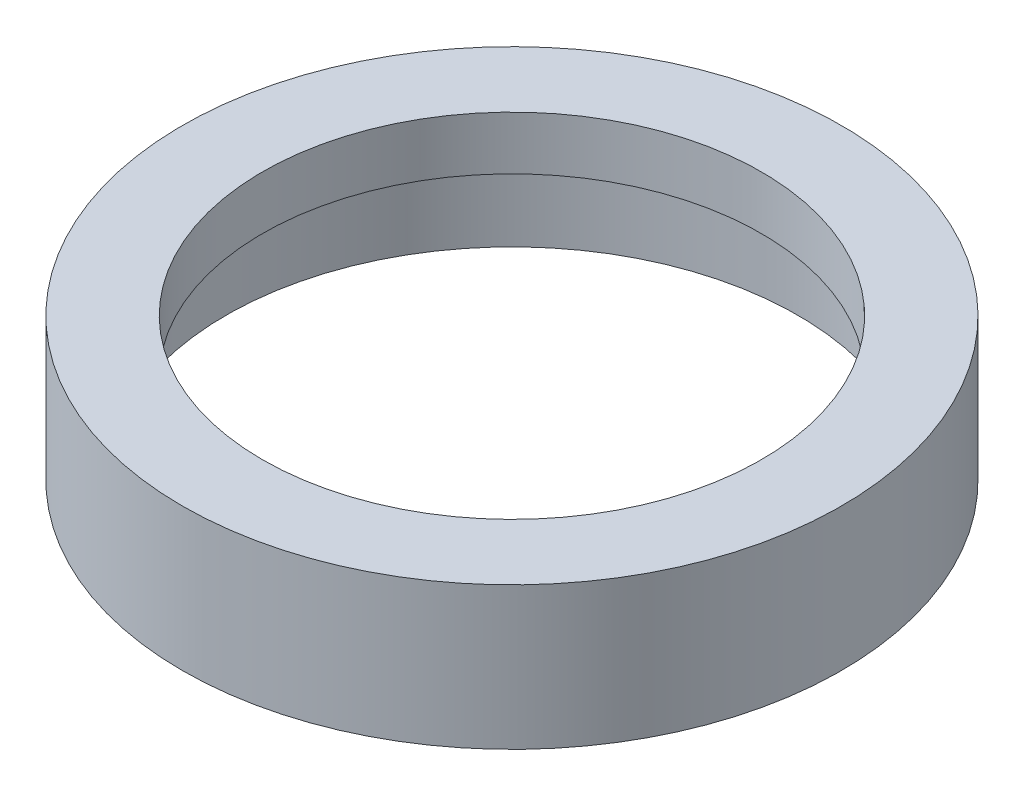
SolidWorks part; units mm, degrees
ref_plane "Front Plane" through (0, 0, 0) normal (0, 0, 1) x (1, 0, 0)
ref_plane "Top Plane" through (0, 0, 0) normal (0, 1, 0) x (1, 0, 0)
ref_plane "Right Plane" through (0, 0, 0) normal (1, 0, 0) x (0, 0, -1)
sketch "Sketch2" plane through (0, 9, 0) normal (0, 1, 0) x (1, 0, 0)
  circle A0 centre (-0.5, 0) radius 18.5 construction
  circle A7 centre (-0.5, 0) radius 18.5
  circle A15 centre (-0.5, 0) radius 16.05
  dimension "D1" = 37
  dimension "D2" = 32.1
extrude "Boss-Extrude1" add sketch "Sketch2" along normal blind 5
sketch "Sketch3" plane through (0, 14, 0) normal (0, 1, 0) x (1, 0, 0)
  circle A0 centre (-0.5, 0) radius 14
  circle A1 centre (-0.5, 0) radius 18.5
extrude "Boss-Extrude2" add sketch "Sketch3" along normal blind 3
